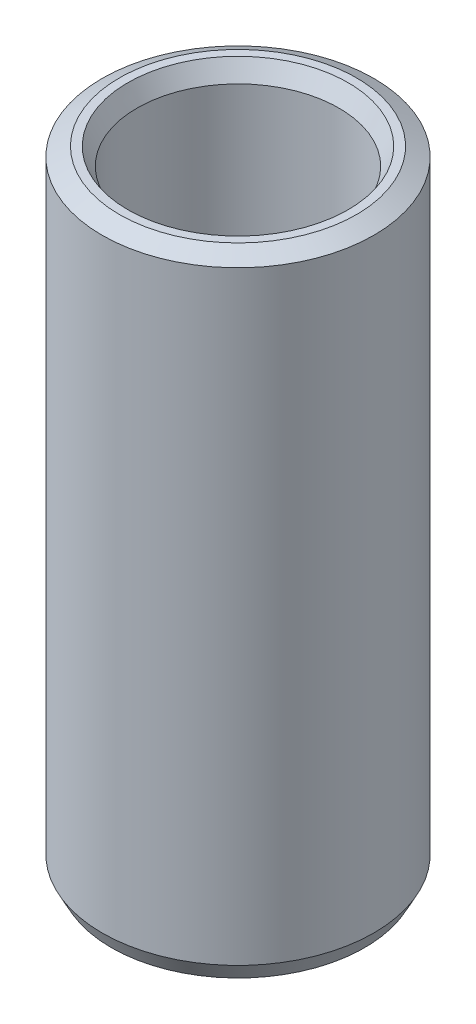
SolidWorks part; units mm, degrees
ref_plane "Front Plane" through (0, 0, 0) normal (0, 0, 1) x (1, 0, 0)
ref_plane "Top Plane" through (0, 0, 0) normal (0, 1, 0) x (1, 0, 0)
ref_plane "Right Plane" through (0, 0, 0) normal (1, 0, 0) x (0, 0, -1)
sketch "Sketch1" plane through (0, 0, 0) normal (0, 1, 0) x (1, 0, 0)
  circle A0 centre (0, 0) radius 50
  dimension "SLEEVE_OD" = 100
extrude "Boss-Extrude1" add sketch "Sketch1" along normal blind 232.1116
sketch "Sketch2" plane through (0, 0, 0) normal (0, 1, 0) x (1, 0, 0)
  circle A0 centre (0, 0) radius 37.1359
  dimension "BORE_D" = 74.2719
extrude "Cut-Extrude1" cut sketch "Sketch2" along normal through all
chamfer "Chamfer1" distance 3.3868 angle 62.106 4 edges at (0, 232.1116, 37.1359) (0, 0, 37.1359) (0, 0, 50) (0, 232.1116, 50) first distance on face at (0, 232.1116, 37.1359) first distance on face at (0, 0, 37.1359) first distance on face at (0, 232.1116, 50)
